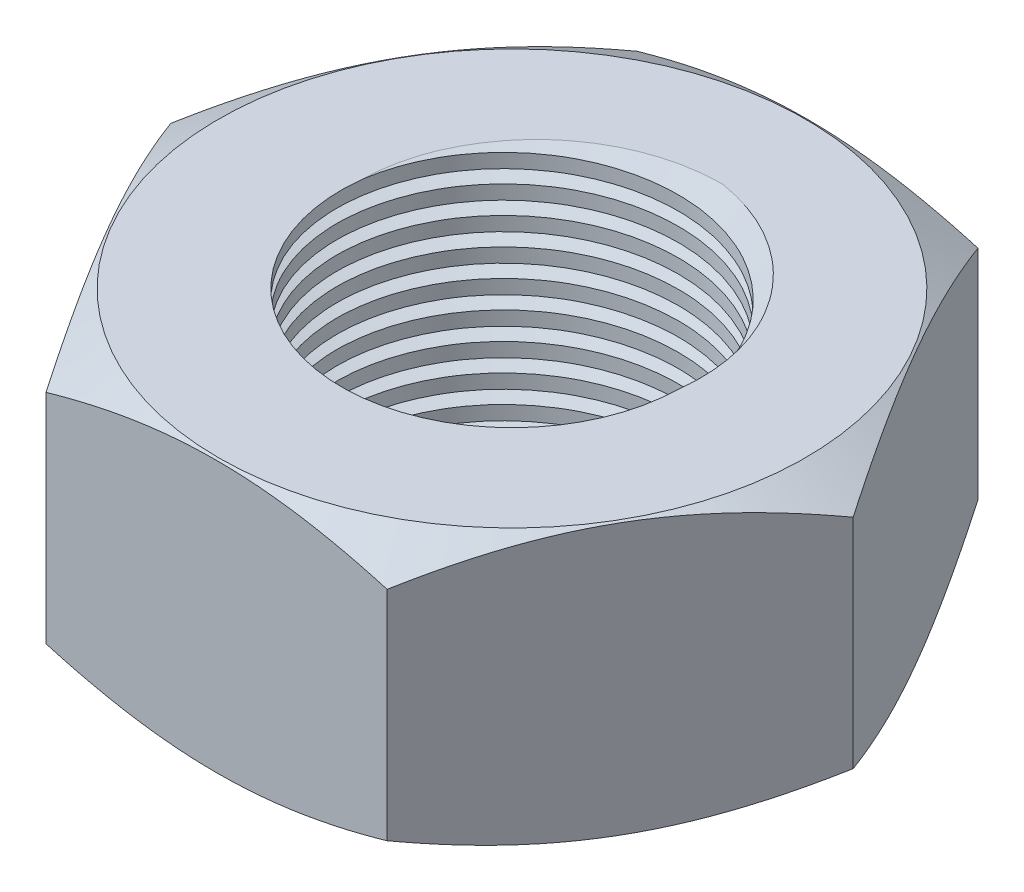
SolidWorks part; units mm, degrees
ref_plane "Front Plane" through (0, 0, 0) normal (0, 0, 1) x (1, 0, 0)
ref_plane "Top Plane" through (0, 0, 0) normal (0, 1, 0) x (1, 0, 0)
ref_plane "Right Plane" through (0, 0, 0) normal (1, 0, 0) x (0, 0, -1)
sketch "Sketch1" plane through (0, 0, 0) normal (0, 1, 0) x (1, 0, 0)
  line L1 (5, 0) -> (2.5, 4.3301)
  line L2 (2.5, 4.3301) -> (-2.5, 4.3301)
  line L3 (-2.5, 4.3301) -> (-5, 0)
  line L4 (-5, 0) -> (-2.5, -4.3301)
  line L5 (-2.5, -4.3301) -> (2.5, -4.3301)
  line L6 (2.5, -4.3301) -> (5, 0)
  circle A0 centre (0, 0) radius 4.3301 construction
  dimension "D1" = 5
extrude "Boss-Extrude1" add sketch "Sketch1" along normal blind 4
sketch "Sketch2" plane through (0, 4, 0) normal (0, 1, 0) x (-1, 0, 0)
  circle A0 centre (0, 0) radius 4.3
  dimension "D1" = 8.6
extrude "Cut-Extrude1" cut sketch "Sketch2" against normal blind 40 draft 60 flip side to cut
sketch "Sketch3" plane through (0, 0, 0) normal (0, -1, 0) x (1, 0, 0)
  circle A0 centre (0, 0) radius 4.3
extrude "Cut-Extrude2" cut sketch "Sketch3" against normal blind 40 draft 60 flip side to cut
sketch "Sketch4" plane through (0, 0, 0) normal (0, -1, 0) x (1, 0, 0)
  circle A0 centre (0, 0) radius 2.5
  dimension "D1" = 5
extrude "Cut-Extrude3" cut sketch "Sketch4" against normal through all
sketch "Sketch5" plane through (0, 0, 0) normal (0, -1, 0) x (1, 0, 0)
  circle A0 centre (0, 0) radius 2.5
curve "Helix/Spiral1" pitch 0.4 height 40 radius 2.5 centre (0, 0, 0) axis (0, 1, 0) start towards (0, 0, -1)
sketch "Sketch6" plane through (0, 0, 0) normal (0, 0, 1) x (1, 0, 0)
  line L0 (2.5, 34.4013) -> (2.5, 34.2078)
  line L1 (2.5, 3.5959) -> (2.5, 0.4041) construction
  line L2 (2.5, 34.2078) -> (2.8755, 34.3045)
  line L3 (2.8755, 34.3045) -> (2.5, 34.4013)
  line L4 (2.5, 3.5959) -> (2.5, 0.4041) construction
sweep "Cut-Sweep3" cut profiles "Sketch6" path "Helix/Spiral1"
